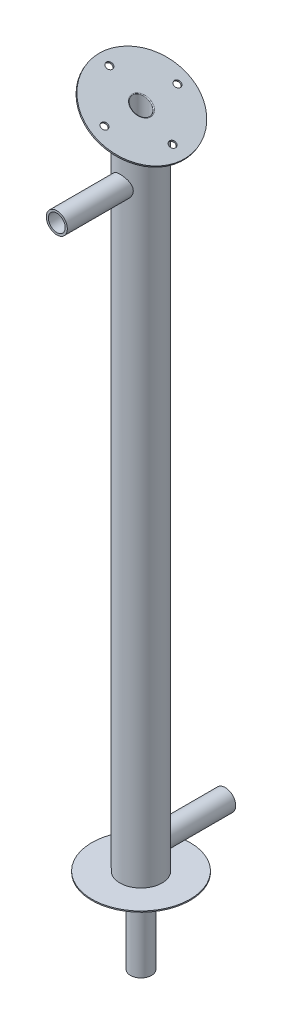
SolidWorks part; units mm, degrees
material "201 Annealed Stainless Steel (SS)"
ref_plane "Front Plane" through (0, 0, 0) normal (0, 0, 1) x (1, 0, 0)
ref_plane "Top Plane" through (0, 0, 0) normal (0, 1, 0) x (1, 0, 0)
ref_plane "Right Plane" through (0, 0, 0) normal (1, 0, 0) x (0, 0, -1)
sketch "Sketch1" plane through (0, 0, 0) normal (0, 1, 0) x (1, 0, 0)
  circle A0 centre (0, 0) radius 19.05
  dimension "D1" = 38.1
extrude "Boss-Extrude1" add sketch "Sketch1" along normal blind 609.6
sketch "Sketch2" plane through (0, 609.6, 0) normal (0, 1, 0) x (1, 0, 0)
  circle A0 centre (0, 0) radius 33.02
  dimension "D1" = 66.04
extrude "Boss-Extrude2" add sketch "Sketch2" along normal blind 1
sketch "Sketch3" plane through (0, 0, 0) normal (0, -1, 0) x (1, 0, 0)
  circle A0 centre (0, 0) radius 44.45
  dimension "D1" = 88.9
extrude "Boss-Extrude3" add sketch "Sketch3" along normal blind 1.016
shell "Shell2" thickness 1 removed face at (0, 610.6, 33.02)
ref_plane "Plane2" through (0, 0, -76.2) normal (0, 0, 1) x (1, 0, 0)
sketch "Sketch6" plane through (0, 0, -76.2) normal (0, 0, 1) x (1, 0, 0)
  circle A0 centre (0, 17.78) radius 9.525
  dimension "D1" = 19.05
  dimension "D2" = 17.78
sketch "Sketch8" plane through (0, -1.016, 0) normal (0, -1, 0) x (1, 0, 0)
  circle A0 centre (0, 0) radius 4
  dimension "D1" = 8
extrude "Cut-Extrude3" cut sketch "Sketch8" against normal up to next
sketch "Sketch9" plane through (0, -1.016, 0) normal (0, -1, 0) x (1, 0, 0)
  circle A0 centre (0, 0) radius 9.525
  dimension "D1" = 19.05
extrude "Boss-Extrude6" add sketch "Sketch9" against normal blind 682.752 from offset 76.2
sketch "Sketch13" plane through (0, 610.6, 0) normal (0, 1, 0) x (1, 0, 0)
  circle A0 centre (33.02, 0) radius 2.032
  circle A1 centre (0, -33.02) radius 2.032
  circle A2 centre (-33.02, 0) radius 2.032
  circle A3 centre (0, 33.02) radius 2.032
  point P12 (0, 0)
  dimension "D1" = 4.064
  dimension "D2" = 33.02
  dimension "D3" = 4
extrude "Cut-Extrude5" cut sketch "Sketch13" against normal up to next
sketch "Sketch16" plane through (0, 0, 0) normal (0, 0, 1) x (1, 0, 0)
  line L0 (-19.05, 609.6) -> (21.9971, 585.9015)
  line L1 (-19.05, 609.6) -> (19.05, 609.6) construction
  line L2 (-32.9575, 609.6) -> (-2.031, 609.6) construction
  line L3 (21.9971, 585.9015) -> (42.636, 621.6492)
  line L4 (42.636, 621.6492) -> (-50.1069, 621.6492)
  line L5 (-50.1069, 621.6492) -> (-50.1069, 605.109)
  line L6 (-50.1069, 605.109) -> (-23.5895, 605.109)
  line L7 (-23.5895, 605.109) -> (-19.05, 609.6)
  dimension "D1" = 30
extrude "Cut-Extrude7" cut sketch "Sketch16" against normal mid plane 203.2
sketch "Sketch17" plane through (259.202, 448.9511, 0) normal (0.5, 0.866, 0) x (0.866, -0.5, 0)
  circle A0 centre (-299.3007, 0) radius 44.45
  dimension "D1" = 88.9
extrude "Boss-Extrude7" add sketch "Sketch17" along normal blind 1.524
sketch "Sketch15" plane through (0, -77.216, 0) normal (0, -1, 0) x (1, 0, 0)
  circle A0 centre (0, 0) radius 7.62
  dimension "D1" = 15.24
extrude "Cut-Extrude6" cut sketch "Sketch15" against normal up to next
sketch "Sketch19" plane through (259.964, 450.2709, 0) normal (0.5, 0.866, 0) x (0.866, -0.5, 0)
  line L0 (-324.1749, 0) -> (-278.3244, 0) construction
  line L1 (-300.1806, 0) -> (-300.1806, 18.1939) construction
  circle A0 centre (-267.1606, 0) radius 3.048
  circle A1 centre (-300.1806, -33.02) radius 3.048
  circle A2 centre (-333.2006, 0) radius 3.048
  circle A3 centre (-300.1806, 33.02) radius 3.048
  point P16 (-300.1806, 0)
  dimension "D1" = 6.096
  dimension "D2" = 33.02
  dimension "D3" = 4
extrude "Cut-Extrude8" cut sketch "Sketch19" against normal up to next
ref_plane "Plane3" through (0, 0, 76.2) normal (0, 0, 1) x (1, 0, 0)
sketch "Sketch20" plane through (0, 0, 76.2) normal (0, 0, 1) x (1, 0, 0)
  circle A0 centre (0, 546.1) radius 9.525
  dimension "D1" = 19.05
  dimension "D2" = 546.1
extrude "Boss-Extrude8" add sketch "Sketch20" against normal up to next
sketch "Sketch21" plane through (0, 0, 76.2) normal (0, 0, 1) x (1, 0, 0)
  circle A0 centre (0, 546.1) radius 7.62
  dimension "D1" = 15.24
extrude "Cut-Extrude9" cut sketch "Sketch21" against normal up to next
extrude "Boss-Extrude9" add sketch "Sketch6" along normal up to next
sketch "Sketch22" plane through (0, 0, -76.2) normal (0, 0, -1) x (-1, 0, 0)
  circle A0 centre (0, 17.78) radius 7.62
  dimension "D1" = 15.24
extrude "Cut-Extrude10" cut sketch "Sketch22" against normal up to next
fillet "Fillet1" radius 0.762 1 edges at (7.62, 595.9618, 0)
